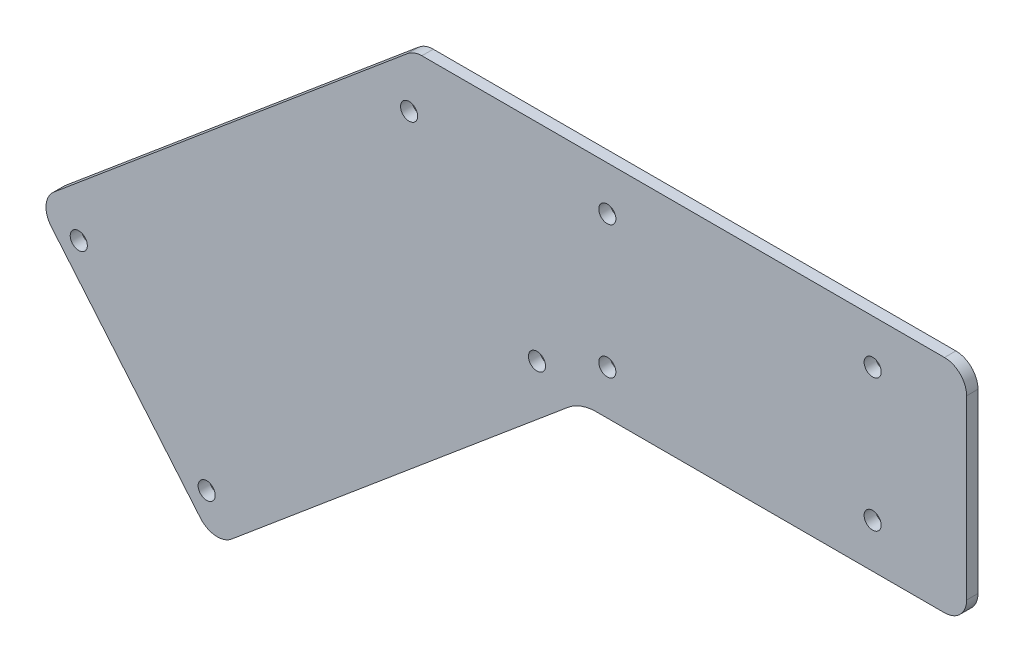
SolidWorks part; units mm, degrees
material "5052-H32"
ref_plane "Front Plane" through (0, 0, 0) normal (0, 0, 1) x (1, 0, 0)
ref_plane "Top Plane" through (0, 0, 0) normal (0, 1, 0) x (1, 0, 0)
ref_plane "Right Plane" through (0, 0, 0) normal (1, 0, 0) x (0, 0, -1)
sketch "Sketch1" plane through (0, 0, 0) normal (0, 0, 1) x (1, 0, 0)
  line L0 (55.5625, 19.05) -> (55.5625, -19.05) construction
  line L1 (0, -31.75) -> (158.75, -31.75)
  line L2 (0, -31.75) -> (0, 31.75)
  line L3 (0, 31.75) -> (158.75, 31.75)
  line L4 (158.75, -31.75) -> (158.75, 31.75)
  line L5 (0, 0) -> (55.5625, 0) construction
  line L6 (131.7625, 19.05) -> (131.7625, -19.05) construction
  line L7 (55.5625, 0) -> (131.7625, 0) construction
  point P4 (0, 0)
  dimension "D1" = 63.5
  dimension "D2" = 158.75
  dimension "D3" = 55.5625
  dimension "D4" = 76.2
  dimension "D5" = 38.1
base flange "Base-Flange1" sketch "Sketch1" thickness 3.2639 reverse thickness direction no parameters "D1"=1.27
hole_wizard "#10 (0.1935) Diameter Hole1" positions "Sketch6" profile "Sketch7" hole size "#10" standard "ANSI Inch" end condition up to next
sketch "Sketch6" plane through (0, 0, 0) normal (0, 0, 1) x (1, 0, 0)
  point P2 (55.5625, 19.05)
  point P5 (55.5625, -19.05)
  point P8 (131.7625, 19.05)
  point P11 (131.7625, -19.05)
sketch "Sketch7" plane through (55.5625, 19.05, 0) normal (1, 0, 0) x (0, -1, 0)
  line L0 (0, 0) -> (0, 3.2639)
  line L1 (0, 3.2639) -> (2.4574, 3.2639)
  line L2 (2.4574, 3.2639) -> (2.4574, 0)
  line L5 (2.4574, 0) -> (0, 0)
  line L11 (0, -6.35) -> (0, 107.95) construction
  dimension "Thru Hole Dia." = 4.9149
  dimension "Thru Hole Depth" = 3.2639
sketch "Sketch8" plane through (0, 0, 0) normal (0, 0, 1) x (1, 0, 0)
  line L0 (0, 31.75) -> (-108.2325, -59.0679)
  line L1 (47.8092, -31.75) -> (-57.2112, -119.8726)
  line L2 (0, -31.75) -> (158.75, -31.75) construction
  line L3 (-57.2112, -119.8726) -> (-108.2325, -59.0679)
  line L4 (0, 31.75) -> (0, -31.75)
  line L5 (0, -31.75) -> (47.8092, -31.75)
  line L6 (0, 31.75) -> (158.75, 31.75) construction
  dimension "D1" = 141.2875
  dimension "D2" = 40
  dimension "D3" = 79.375
extrude "Boss-Extrude1" add sketch "Sketch8" against normal up to surface (3.2639 mm away) up to face at (53.1051, 19.05, -3.2639)
sketch "Sketch12" plane through (0, 0, 0) normal (0, 0, 1) x (1, 0, 0)
  line L0 (-96.2251, -63.4988) -> (-1.3697, 16.0944) construction
  line L1 (0, 31.75) -> (-108.2325, -59.0679) construction
  line L2 (-108.2325, -59.0679) -> (-57.2112, -119.8726) construction
  line L3 (-1.3697, 16.0944) -> (35.3656, -27.6851) construction
  line L4 (35.3656, -27.6851) -> (-59.4898, -107.2783) construction
  line L5 (-59.4898, -107.2783) -> (-96.2251, -63.4988) construction
  line L6 (-57.2112, -119.8726) -> (47.8092, -31.75) construction
  line L7 (18.5286, -7.6195) -> (-76.3269, -87.2127) construction
  dimension "D1" = 6.35
  dimension "D2" = 123.825
  dimension "D3" = 11.1125
  dimension "D4" = 11.1125
  dimension "D5" = 26.1937
  dimension "D7" = 30.9563
hole_wizard "#10 (0.1935) Diameter Hole2" positions "Sketch13" profile "Sketch14" hole size "#10" standard "ANSI Inch" end condition up to next
sketch "Sketch13" plane through (0, 0, 0) normal (0, 0, 1) x (1, 0, 0)
  point P0 (-1.3697, 16.0944)
  point P3 (-96.2251, -63.4988)
  point P6 (35.3656, -27.6851)
  point P9 (-59.4898, -107.2783)
sketch "Sketch14" plane through (-1.3697, 16.0944, 0) normal (1, 0, 0) x (0, -1, 0)
  line L0 (0, 0) -> (0, 3.2639)
  line L1 (0, 3.2639) -> (2.4574, 3.2639)
  line L2 (2.4574, 3.2639) -> (2.4574, 0)
  line L5 (2.4574, 0) -> (0, 0)
  line L11 (0, -6.35) -> (0, 107.95) construction
  dimension "Thru Hole Dia." = 4.9149
  dimension "Thru Hole Depth" = 3.2639
fillet "Fillet1" radius 6.35 5 edges at (158.75, -31.75, -1.632) (158.75, 31.75, -1.632) (0, 31.75, -1.632) (-108.2325, -59.0679, -1.6319) (-57.2112, -119.8726, -1.6319)
fillet "Fillet2" radius 12.7 1 edges at (47.8092, -31.75, -1.632)
sketch "Bend-Lines1" [suppressed] plane through (0, 0, 0) normal (0, 1, 0) x (1, 0, 0)
sketch "Bounding-Box1" [suppressed] plane through (0, 0, 0) normal (0, 1, 0) x (1, 0, 0)
sheet metal parameters "Sheet-Metal1" thickness 3.2639 parameters "D1"=1.27
flat pattern "Flat-Pattern1" [suppressed]
sketch "Bend-Lines2" plane through (0, 0, 0) normal (0, 1, 0) x (1, 0, 0)
sketch3d "Bounding-Box2" [suppressed]
  line L0 (0, -32.6581, 0) -> (-114.3, -32.6581, 0) construction
  line L1 (0, 32.6581, 0) -> (-114.3, 32.6581, 0) construction
  line L2 (0, -32.6581, 0) -> (0, 32.6581, 0) construction
  line L3 (-114.3, -32.6581, 0) -> (-114.3, 32.6581, 0) construction
sheet metal parameters "Sheet-Metal2" thickness 3.2639 parameters "D1"=1.27
flat pattern "Flat-Pattern1"
sketch "Bend-Lines2" plane through (0, 0, 0) normal (0, 1, 0) x (1, 0, 0)
sketch3d "Bounding-Box2" [suppressed]
  line L0 (0, -32.6581, 0) -> (114.3, -32.6581, 0) construction
  line L1 (0, 32.6581, 0) -> (114.3, 32.6581, 0) construction
  line L2 (0, -32.6581, 0) -> (0, 32.6581, 0) construction
  line L3 (114.3, -32.6581, 0) -> (114.3, 32.6581, 0) construction
sheet metal parameters "Sheet-Metal3" thickness 3.2639 parameters "D1"=1.27
flat pattern "Flat-Pattern1"
sketch "Bend-Lines2" plane through (0, 0, 0) normal (0, 1, 0) x (1, 0, 0)
sketch3d "Bounding-Box2" [suppressed]
  line L0 (-78.5981, -166.7639, 0) -> (144.9128, -11.3755, 0) construction
  line L1 (-146.4543, -69.1594, 0) -> (77.0566, 86.229, 0) construction
  line L2 (-78.5981, -166.7639, 0) -> (-146.4543, -69.1594, 0) construction
  line L3 (144.9128, -11.3755, 0) -> (77.0566, 86.229, 0) construction
sheet metal parameters "Sheet-Metal5" thickness 3.2639 parameters "D1"=1.27
flat pattern "Flat-Pattern1"
sketch "Bend-Lines2" plane through (0, 0, 0) normal (0, 1, 0) x (1, 0, 0)
sketch3d "Bounding-Box2" [suppressed]
  line L0 (-78.6862, -126.9042, 0) -> (178.4997, -21.5726, 0) construction
  line L1 (-122.8752, -19.0088, 0) -> (134.3107, 86.3228, 0) construction
  line L2 (-78.6862, -126.9042, 0) -> (-122.8752, -19.0088, 0) construction
  line L3 (178.4997, -21.5726, 0) -> (134.3107, 86.3228, 0) construction
